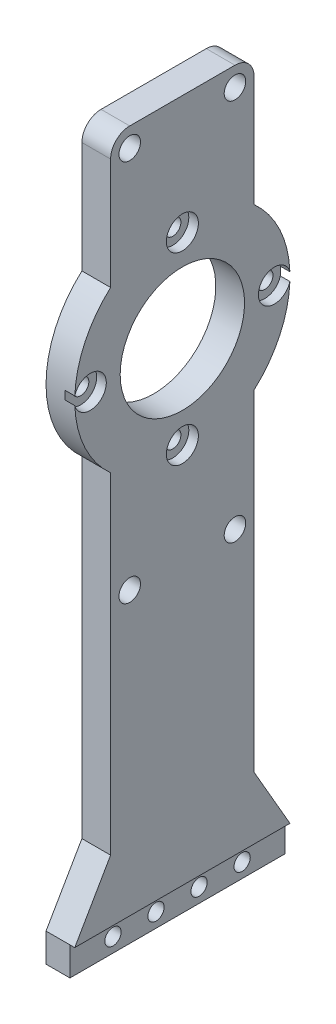
SolidWorks part; units mm, degrees
material "Сплав 2024"
ref_plane "Спереди" through (0, 0, 0) normal (0, 0, 1) x (1, 0, 0)
ref_plane "Сверху" through (0, 0, 0) normal (0, 1, 0) x (1, 0, 0)
ref_plane "Справа" through (0, 0, 0) normal (1, 0, 0) x (0, 0, -1)
sketch "Эскиз1" plane through (0, 0, 0) normal (0, 1, 0) x (1, 0, 0)
  line L1 (0, 0) -> (6, 0)
  line L2 (0, 0) -> (0, -30)
  line L3 (0, -30) -> (6, -30)
  line L4 (6, 0) -> (6, -30)
  dimension "D1" = 6
  dimension "D2" = 30
extrude "Бобышка-Вытянуть1" add sketch "Эскиз1" along normal blind 177
sketch "Эскиз2" plane through (0, 0, 0) normal (-1, 0, 0) x (0, 0, 1)
  line L0 (30, 105) -> (0, 105) construction
  line L3 (15, 177) -> (15, 0) construction
  line L4 (0, 177) -> (30, 177) construction
  line L5 (0, 0) -> (30, 0) construction
  line L6 (30, 0) -> (0, 0) construction
  circle A0 centre (15, 105) radius 22.5
  dimension "D1" = 45
  dimension "D2" = 105
extrude "Бобышка-Вытянуть2" add sketch "Эскиз2" against normal up to surface (6 mm away) up to face at (6, 88.5, 15)
sketch "Эскиз3" plane through (0, 0, 0) normal (-1, 0, 0) x (0, 0, 1)
  circle A0 centre (15, 105) radius 13
  dimension "D1" = 26
extrude "Вырез-Вытянуть1" cut sketch "Эскиз3" against normal through all
sketch "Эскиз4" plane through (6, 0, 0) normal (-1, 0, 0) x (0, 0, 1)
  line L0 (15, 127.5) -> (15, 82.5) construction
  line L1 (15, 177) -> (15, 0) construction
  line L2 (37.5, 105) -> (-7.5, 105) construction
  circle A0 centre (15, 105) radius 19.25 construction
  circle A1 centre (15, 105) radius 22.5 construction
  dimension "D1" = 38.5
hole_wizard "Цековка для  винта с полукруглой головкой M31" positions "Эскиз6" profile "Эскиз5" counterbore size "M3" standard "Ansi Metric" end condition through all
sketch "Эскиз6" plane through (6, -25.0247, 7.2629) normal (-1, 0, 0) x (0, 0, 1)
  line L0 (7.7371, 152.5247) -> (7.7371, 107.5247) construction
  line L1 (30.2371, 130.0247) -> (-14.7629, 130.0247) construction
  circle A0 centre (7.7371, 130.0247) radius 19.25 construction
  point P0 (7.7371, 149.2747)
  point P6 (-11.5129, 130.0247)
  point P10 (7.7371, 110.7747)
  point P12 (26.9871, 130.0247)
sketch "Эскиз5" plane through (6, 124.25, 15) normal (0, 1, 0) x (0, 0, -1)
  line L0 (0, 0) -> (0, 6)
  line L1 (0, 6) -> (1.7, 6)
  line L3 (1.7, 6) -> (1.7, 2)
  line L4 (1.7, 2) -> (3.35, 2)
  line L5 (3.35, 2) -> (3.35, 0)
  line L7 (3.35, 0) -> (0, 0)
  line L11 (0, -6.35) -> (0, 107.95) construction
  dimension "Диаметр сквозного отверстия" = 3.4
  dimension "Глубина сквозного отверстия" = 6
  dimension "Диаметр цековки" = 6.7
  dimension "Глубина цековки" = 2
sketch "Эскиз8" plane through (6, 0, 0) normal (1, 0, 0) x (0, 0, -1)
  line L0 (-15, 177) -> (-15, 0) construction
  line L1 (-30, 177) -> (0, 177) construction
  line L2 (-30, 0) -> (0, 0) construction
  line L3 (19.447, 105) -> (-49.447, 105) construction
  line L4 (0, 177) -> (0, 121.7705) construction
  line L5 (-26, 145) -> (-4, 145) construction
  line L6 (-26, 145) -> (-26, 65) construction
  line L7 (-26, 65) -> (-4, 65) construction
  line L8 (-4, 145) -> (-4, 65) construction
  line L9 (-26, 145) -> (-4, 65) construction
  line L10 (-26, 65) -> (-4, 145) construction
  line L11 (-30, 105) -> (0, 105) construction
  point P8 (-15, 105)
  point P9 (-15, 105)
  dimension "D1" = 4
  dimension "D2" = 80
hole_wizard "Отверстие с зазором M41" positions "Эскиз10" profile "Эскиз9" hole size "M4" standard "Ansi Metric" end condition through all
sketch "Эскиз10" plane through (6, 0, 0) normal (1, 0, 0) x (0, 0, -1)
  point P0 (-26, 145)
  point P3 (-4, 145)
  point P6 (-4, 65)
  point P9 (-26, 65)
sketch "Эскиз9" plane through (6, 145, 26) normal (0, 1, 0) x (0, 0, -1)
  line L0 (0, 0) -> (0, 6)
  line L1 (0, 6) -> (2.25, 6)
  line L2 (2.25, 6) -> (2.25, 0)
  line L5 (2.25, 0) -> (0, 0)
  line L11 (0, -6.35) -> (0, 107.95) construction
  dimension "Диаметр сквозного отверстия" = 4.5
  dimension "Глубина сквозного отверстия" = 6
sketch "Эскиз11" plane through (6, 0, 0) normal (1, 0, 0) x (0, 0, -1)
  line L0 (-30, 0) -> (0, 0) construction
  line L1 (-15, 177) -> (-15, 0) construction
  line L2 (-30, 177) -> (0, 177) construction
  line L3 (0, 88.2295) -> (0, 0) construction
  line L4 (-30, 88.2295) -> (-30, 0) construction
  line L5 (-37.5, 3) -> (7.5, 3) construction
  line L20 (-1.5, 0) -> (-1.5, 6) construction
  line L21 (-10.5, 0) -> (-10.5, 6) construction
  line L22 (-19.5, 0) -> (-19.5, 6) construction
  line L23 (-28.5, 0) -> (-28.5, 6) construction
  line L25 (-37.5, 0) -> (7.5, 6) construction
  line L26 (-37.5, 6) -> (7.5, 0) construction
  line L27 (-37.5, 6) -> (7.5, 6) construction
  line L28 (0, 18.9904) -> (7.5, 6)
  line L29 (-30, 18.9904) -> (0, 18.9904)
  line L30 (7.5, 6) -> (7.5, 0)
  line L31 (-37.5, 0) -> (7.5, 0)
  line L32 (-37.5, 6) -> (-37.5, 0)
  line L33 (-37.5, 6) -> (-30, 18.9904)
  point P2 (-15, 3)
  dimension "D1" = 45
  dimension "D2" = 6
  dimension "D3" = 9
  dimension "D4" = 9
  dimension "D5" = 9
  dimension "D6" = 9
  dimension "D7" = 120
extrude "Бобышка-Вытянуть3" add sketch "Эскиз11" against normal up to surface (6 mm away) up to face at (0, 145, 23.75)
hole_wizard "Отверстие с зазором M31" positions "Эскиз13" profile "Эскиз12" hole size "M3" standard "Ansi Metric" end condition through all
sketch "Эскиз13" plane through (6, 0, 0) normal (1, 0, 0) x (0, 0, -1)
  line L4 (-28.5, 0) -> (-28.5, 6) construction
  line L5 (-19.5, 0) -> (-19.5, 6) construction
  line L6 (-10.5, 0) -> (-10.5, 6) construction
  line L7 (-1.5, 0) -> (-1.5, 6) construction
  point P16 (-28.5, 3)
  point P20 (-19.5, 3)
  point P24 (-10.5, 3)
  point P28 (-1.5, 3)
sketch "Эскиз12" plane through (6, 3, 28.5) normal (0, 1, 0) x (0, 0, -1)
  line L0 (0, 0) -> (0, 6)
  line L1 (0, 6) -> (1.7, 6)
  line L2 (1.7, 6) -> (1.7, 0)
  line L5 (1.7, 0) -> (0, 0)
  line L11 (0, -6.35) -> (0, 107.95) construction
  dimension "Диаметр сквозного отверстия" = 3.4
  dimension "Глубина сквозного отверстия" = 6
sketch "Эскиз14" plane through (6, 0, 0) normal (1, 0, 0) x (0, 0, -1)
  line L5 (-37.5, 0) -> (7.5, 0)
  line L6 (-37.5, 0) -> (-37.5, 6)
  line L7 (-37.5, 6) -> (7.5, 6)
  line L8 (7.5, 0) -> (7.5, 6)
extrude "Вырез-Вытянуть2" cut sketch "Эскиз14" against normal blind 1
sketch "Эскиз15" plane through (6, 0, 0) normal (1, 0, 0) x (0, 0, -1)
  line L0 (0, 177) -> (0, 121.7705) construction
  line L1 (-30, 177) -> (0, 177)
  line L2 (-30, 177) -> (-30, 149.0245)
  line L3 (-30, 149.0245) -> (0, 149.0245)
  line L4 (0, 177) -> (0, 149.0245)
  circle A0 centre (-26, 145) radius 2.25 construction
  dimension "D1" = 4.0245
extrude "Вырез-Вытянуть3" cut sketch "Эскиз15" against normal up to surface (6 mm away) up to face at (0, 3, 26.8)
fillet "Скругление1" radius 4 2 edges at (3, 149.0245, 30) (3, 149.0245, 0)
equation "\"D4@Эскиз11\"=\"D3@Эскиз11\""
equation "\"D5@Эскиз11\"=\"D3@Эскиз11\""
equation "\"D6@Эскиз11\"=\"D4@Эскиз11\""
equation "\"D3@Эскиз11\" = \"D1@Эскиз11\" / 5"
